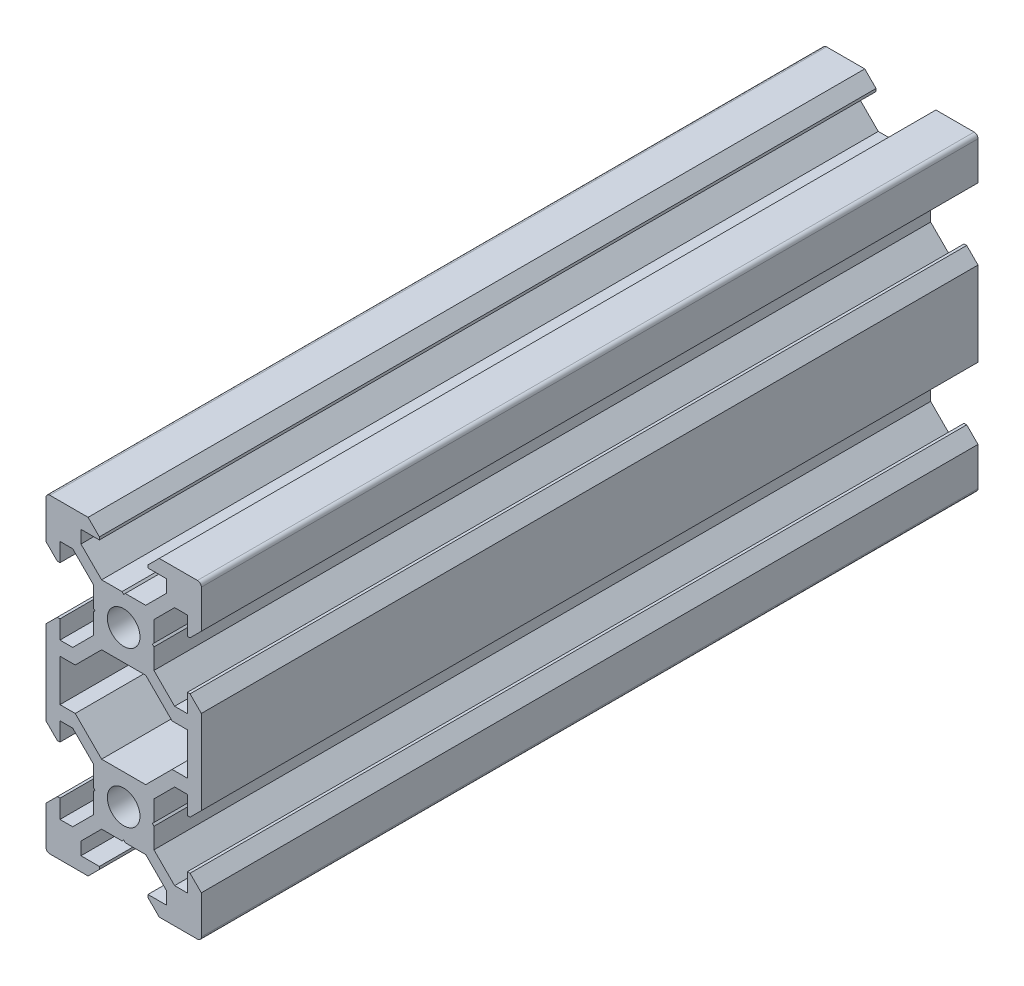
SolidWorks part; units mm, degrees
material "6061-T6 (SS)"
ref_plane "Front Plane" through (0, 0, 0) normal (0, 0, 1) x (1, 0, 0)
ref_plane "Top Plane" through (0, 0, 0) normal (0, 1, 0) x (1, 0, 0)
ref_plane "Right Plane" through (0, 0, 0) normal (1, 0, 0) x (0, 0, -1)
sketch "Sketch1" plane through (0, 0, 0) normal (0, 0, 1) x (1, 0, 0)
  line L0 (0, 0) -> (10, 0) construction
  line L1 (9.5, -20) -> (-9.5, -20)
  line L2 (10, -19.5) -> (10, 19.5)
  line L3 (9.5, 20) -> (-9.5, 20)
  line L4 (-10, -19.5) -> (-10, 19.5)
  line L5 (10, -20) -> (-10, 20) construction
  line L6 (10, 20) -> (-10, -20) construction
  circle A0 centre (0, 10) radius 2.1
  circle A1 centre (0, -10) radius 2.1
  arc A2 (-9.5, -20) -> (-10, -19.5) centre (-9.5, -19.5) cw
  arc A3 (9.5, -20) -> (10, -19.5) centre (9.5, -19.5) ccw
  arc A4 (10, 19.5) -> (9.5, 20) centre (9.5, 19.5) ccw
  arc A5 (-9.5, 20) -> (-10, 19.5) centre (-9.5, 19.5) ccw
  point P0 (0, 0)
  line B0 (0, 10) -> (0, 20) construction
  line B1 (0, 13.69) -> (-0.21, 13.9)
  line B2 (-0.21, 13.9) -> (-2.8393, 13.9)
  line B3 (-2.8393, 13.9) -> (-5.5, 16.5607)
  line B4 (-5.5, 16.5607) -> (-5.5, 18.2)
  line B5 (-5.5, 18.2) -> (-3.125, 18.2)
  line B6 (-3.125, 18.2) -> (-3.125, 18.545)
  line B7 (-3.125, 18.545) -> (-4.58, 20)
  line B8 (-4.58, 20) -> (4.58, 20)
  line B9 (0, 10) -> (-5.9132, 15.9132) construction
  line B10 (3.125, 18.545) -> (4.58, 20)
  line B11 (3.125, 18.2) -> (3.125, 18.545)
  line B12 (5.5, 18.2) -> (3.125, 18.2)
  line B13 (5.5, 16.5607) -> (5.5, 18.2)
  line B14 (2.8393, 13.9) -> (5.5, 16.5607)
  line B15 (0.21, 13.9) -> (2.8393, 13.9)
  line B16 (0, 13.69) -> (0.21, 13.9)
  line B17 (0, 10) -> (-10, 10) construction
  line B18 (-3.69, 10) -> (-3.9, 9.79)
  line B19 (-3.9, 9.79) -> (-3.9, 7.1607)
  line B20 (-3.9, 7.1607) -> (-6.5607, 4.5)
  line B21 (-6.5607, 4.5) -> (-8.2, 4.5)
  line B22 (-8.2, 4.5) -> (-8.2, 6.875)
  line B23 (-8.2, 6.875) -> (-8.545, 6.875)
  line B24 (-8.545, 6.875) -> (-10, 5.42)
  line B25 (-10, 5.42) -> (-10, 14.58)
  line B26 (0, 10) -> (-5.9132, 4.0868) construction
  line B27 (-8.545, 13.125) -> (-10, 14.58)
  line B28 (-8.2, 13.125) -> (-8.545, 13.125)
  line B29 (-8.2, 15.5) -> (-8.2, 13.125)
  line B30 (-6.5607, 15.5) -> (-8.2, 15.5)
  line B31 (-3.9, 12.8393) -> (-6.5607, 15.5)
  line B32 (-3.9, 10.21) -> (-3.9, 12.8393)
  line B33 (-3.69, 10) -> (-3.9, 10.21)
  line B34 (0, -10) -> (-10, -10) construction
  line B35 (-3.69, -10) -> (-3.9, -10.21)
  line B36 (-3.9, -10.21) -> (-3.9, -12.8393)
  line B37 (-3.9, -12.8393) -> (-6.5607, -15.5)
  line B38 (-6.5607, -15.5) -> (-8.2, -15.5)
  line B39 (-8.2, -15.5) -> (-8.2, -13.125)
  line B40 (-8.2, -13.125) -> (-8.545, -13.125)
  line B41 (-8.545, -13.125) -> (-10, -14.58)
  line B42 (-10, -14.58) -> (-10, -5.42)
  line B43 (0, -10) -> (-5.9132, -15.9132) construction
  line B44 (-8.545, -6.875) -> (-10, -5.42)
  line B45 (-8.2, -6.875) -> (-8.545, -6.875)
  line B46 (-8.2, -4.5) -> (-8.2, -6.875)
  line B47 (-6.5607, -4.5) -> (-8.2, -4.5)
  line B48 (-3.9, -7.1607) -> (-6.5607, -4.5)
  line B49 (-3.9, -9.79) -> (-3.9, -7.1607)
  line B50 (-3.69, -10) -> (-3.9, -9.79)
  line B51 (0, -10) -> (0, -20) construction
  line B52 (0, -13.69) -> (0.21, -13.9)
  line B53 (0.21, -13.9) -> (2.8393, -13.9)
  line B54 (2.8393, -13.9) -> (5.5, -16.5607)
  line B55 (5.5, -16.5607) -> (5.5, -18.2)
  line B56 (5.5, -18.2) -> (3.125, -18.2)
  line B57 (3.125, -18.2) -> (3.125, -18.545)
  line B58 (3.125, -18.545) -> (4.58, -20)
  line B59 (4.58, -20) -> (-4.58, -20)
  line B60 (0, -10) -> (5.9132, -15.9132) construction
  line B61 (-3.125, -18.545) -> (-4.58, -20)
  line B62 (-3.125, -18.2) -> (-3.125, -18.545)
  line B63 (-5.5, -18.2) -> (-3.125, -18.2)
  line B64 (-5.5, -16.5607) -> (-5.5, -18.2)
  line B65 (-2.8393, -13.9) -> (-5.5, -16.5607)
  line B66 (-0.21, -13.9) -> (-2.8393, -13.9)
  line B67 (0, -13.69) -> (-0.21, -13.9)
  line B68 (0, -10) -> (10, -10) construction
  line B69 (3.69, -10) -> (3.9, -9.79)
  line B70 (3.9, -9.79) -> (3.9, -7.1607)
  line B71 (3.9, -7.1607) -> (6.5607, -4.5)
  line B72 (6.5607, -4.5) -> (8.2, -4.5)
  line B73 (8.2, -4.5) -> (8.2, -6.875)
  line B74 (8.2, -6.875) -> (8.545, -6.875)
  line B75 (8.545, -6.875) -> (10, -5.42)
  line B76 (10, -5.42) -> (10, -14.58)
  line B77 (0, -10) -> (5.9132, -4.0868) construction
  line B78 (8.545, -13.125) -> (10, -14.58)
  line B79 (8.2, -13.125) -> (8.545, -13.125)
  line B80 (8.2, -15.5) -> (8.2, -13.125)
  line B81 (6.5607, -15.5) -> (8.2, -15.5)
  line B82 (3.9, -12.8393) -> (6.5607, -15.5)
  line B83 (3.9, -10.21) -> (3.9, -12.8393)
  line B84 (3.69, -10) -> (3.9, -10.21)
  line B85 (0, 10) -> (10, 10) construction
  line B86 (3.69, 10) -> (3.9, 10.21)
  line B87 (3.9, 10.21) -> (3.9, 12.8393)
  line B88 (3.9, 12.8393) -> (6.5607, 15.5)
  line B89 (6.5607, 15.5) -> (8.2, 15.5)
  line B90 (8.2, 15.5) -> (8.2, 13.125)
  line B91 (8.2, 13.125) -> (8.545, 13.125)
  line B92 (8.545, 13.125) -> (10, 14.58)
  line B93 (10, 14.58) -> (10, 5.42)
  line B94 (0, 10) -> (5.9132, 15.9132) construction
  line B95 (8.545, 6.875) -> (10, 5.42)
  line B96 (8.2, 6.875) -> (8.545, 6.875)
  line B97 (8.2, 4.5) -> (8.2, 6.875)
  line B98 (6.5607, 4.5) -> (8.2, 4.5)
  line B99 (3.9, 7.1607) -> (6.5607, 4.5)
  line B100 (3.9, 9.79) -> (3.9, 7.1607)
  line B101 (3.69, 10) -> (3.9, 9.79)
  line B102 (-8.2, -2.7) -> (-8.2, 2.7)
  line B103 (-8.2, 2.7) -> (-6.2393, 2.7)
  line B104 (-6.2393, 2.7) -> (-2.8393, 6.1)
  line B105 (-2.8393, 6.1) -> (2.8393, 6.1)
  line B106 (0, 6.1) -> (0, 0) construction
  line B107 (0, 0) -> (-8.2, 0) construction
  line B108 (6.2393, 2.7) -> (2.8393, 6.1)
  line B109 (8.2, 2.7) -> (6.2393, 2.7)
  line B110 (8.2, -2.7) -> (8.2, 2.7)
  line B111 (8.2, -2.7) -> (6.2393, -2.7)
  line B112 (6.2393, -2.7) -> (2.8393, -6.1)
  line B113 (-2.8393, -6.1) -> (2.8393, -6.1)
  line B114 (-6.2393, -2.7) -> (-2.8393, -6.1)
  line B115 (-8.2, -2.7) -> (-6.2393, -2.7)
  line B116 (0, 6.1) -> (0, 10) construction
  line B117 (0, 10) -> (-5.0927, 4.9073) construction
  dimension "D4" = 4.2
  dimension "D5" = 0.5
  dimension "D1" = 20
  dimension "D2" = 40
  dimension "D3" = 20
sketch_block_instance "V Slot 1-4"
sketch_block "V Slot 1" parameters "D1"=10, "D2"=11, "D3"=4.3, "D4"=1.8, "D5"=0.21, "D6"=45, "D7"=9.16, "D8"=1.5, "D9"=6.25
sketch_block_instance "V Slot 1-5"
sketch_block_instance "V Slot 1-6"
sketch_block_instance "V Slot 1-7"
sketch_block_instance "V Slot 1-8"
sketch_block_instance "V Slot 1-9"
sketch_block_instance "Center Cutout 1-1"
sketch_block "Center Cutout 1" parameters "D1"=5.4, "D2"=12.2, "D3"=8.2, "D4"=45, "D5"=10, "D6"=1.5
extrude "Boss-Extrude1" add sketch "Sketch1" along normal blind 100 contours B101 B86 B87 B88 B89 B90 B91 B92 L2 A4 L3 B10 B11 B12 B13 B14 B15 B16 B1 B2 B3 B4 B5 B6 B7 A5 L4 B27 B28 B29 B30 B31 B32 B33 B18 B19 B20 B21 B22 B23 B24 B44 B45 B46 B47 B48 B49 B50 B35 region at (7.04, -19.5528, 0)
